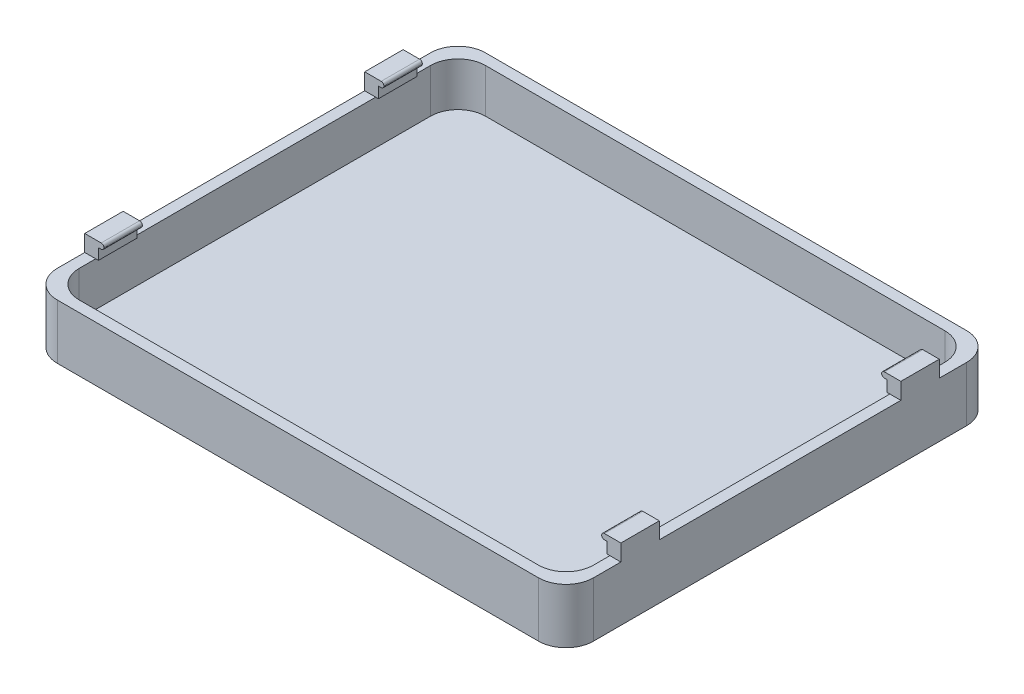
SolidWorks part; units mm, degrees
ref_plane "Front Plane" through (0, 0, 0) normal (0, 0, 1) x (1, 0, 0)
ref_plane "Top Plane" through (0, 0, 0) normal (0, 1, 0) x (1, 0, 0)
ref_plane "Right Plane" through (0, 0, 0) normal (1, 0, 0) x (0, 0, -1)
sketch "Sketch1" plane through (0, 0, 0) normal (0, 1, 0) x (1, 0, 0)
  line L1 (-48.85, 0) -> (48.85, 0)
  line L2 (-48.85, 0) -> (-48.85, -78.02)
  line L3 (-48.85, -78.02) -> (48.85, -78.02)
  line L4 (48.85, 0) -> (48.85, -78.02)
  point P4 (0, 0)
  dimension "D1" = 97.7
  dimension "D2" = 78.02
extrude "Boss-Extrude1" add sketch "Sketch1" along normal blind 10
sketch "Sketch2" plane through (0, 10, 0) normal (0, 1, 0) x (1, 0, 0)
  line L0 (-48.85, 0) -> (-48.85, -78.02) construction
  line L1 (-48.85, -10) -> (-46.35, -10)
  line L2 (-48.85, -10) -> (-48.85, -17)
  line L3 (-48.85, -17) -> (-46.35, -17)
  line L4 (-46.35, -10) -> (-46.35, -17)
  line L5 (48.85, 0) -> (-48.85, 0) construction
  line L6 (0, -5.5) -> (0, 5.5) construction
  line L7 (46.35, -10) -> (46.35, -17)
  line L8 (48.85, -17) -> (46.35, -17)
  line L9 (48.85, -10) -> (48.85, -17)
  line L10 (48.85, -10) -> (46.35, -10)
  line L11 (-76.3487, -39.01) -> (69.8401, -39.01) construction
  line L12 (48.85, 0) -> (-48.85, 0) construction
  line L13 (48.85, -68.02) -> (46.35, -68.02)
  line L14 (48.85, -68.02) -> (48.85, -61.02)
  line L15 (48.85, -61.02) -> (46.35, -61.02)
  line L16 (46.35, -68.02) -> (46.35, -61.02)
  line L17 (-46.35, -68.02) -> (-46.35, -61.02)
  line L18 (-48.85, -61.02) -> (-46.35, -61.02)
  line L19 (-48.85, -68.02) -> (-48.85, -61.02)
  line L20 (-48.85, -68.02) -> (-46.35, -68.02)
  dimension "D1" = 10
  dimension "D2" = 7
  dimension "D3" = 2.5
  dimension "D4" = 39.01
extrude "Boss-Extrude2" add sketch "Sketch2" along normal blind 3
sketch "Sketch3" plane through (-46.35, 0, 0) normal (1, 0, 0) x (0, 0, -1)
  line L0 (-10, 13) -> (-10, 10) construction
  line L1 (-17, 13) -> (-10, 13)
  line L2 (-17, 13) -> (-17, 12)
  line L3 (-17, 12) -> (-10, 12)
  line L4 (-10, 13) -> (-10, 12)
  line L5 (-61.02, 13) -> (-61.02, 10) construction
  line L6 (-68.02, 13) -> (-61.02, 13)
  line L7 (-68.02, 13) -> (-68.02, 12)
  line L8 (-68.02, 12) -> (-61.02, 12)
  line L9 (-61.02, 13) -> (-61.02, 12)
  dimension "D1" = 1
  dimension "D2" = 1
extrude "Boss-Extrude3" add sketch "Sketch3" along normal blind 1
sketch "Sketch4" plane through (46.35, 0, 0) normal (-1, 0, 0) x (0, 0, 1)
  line L1 (10, 13) -> (17, 13)
  line L2 (10, 13) -> (10, 12)
  line L3 (10, 12) -> (17, 12)
  line L4 (17, 13) -> (17, 12)
  line L6 (61.02, 13) -> (68.02, 13)
  line L7 (61.02, 13) -> (61.02, 12)
  line L8 (61.02, 12) -> (68.02, 12)
  line L9 (68.02, 13) -> (68.02, 12)
  line L10 (17, 13) -> (17, 10) construction
  line L12 (68.02, 13) -> (68.02, 10) construction
  point P5 (0, 0)
  point P12 (0, 0)
  point P13 (0, 0)
  point P15 (0, 0)
  dimension "D1" = 1
  dimension "D2" = 1
extrude "Boss-Extrude4" add sketch "Sketch4" along normal blind 1
fillet "Fillet1" radius 0.5 8 edges at (45.35, 13, 13.5) (45.35, 12, 13.5) (45.35, 12, 64.52) (45.35, 13, 64.52) (-45.35, 12, 13.5) (-45.35, 13, 13.5) (-45.35, 12, 64.52) (-45.35, 13, 64.52)
sketch "Sketch5" plane through (0, 10, 0) normal (0, 1, 0) x (1, 0, 0)
  line L0 (48.85, -61.02) -> (48.85, -17) construction
  line L1 (-46.85, -2) -> (46.85, -2)
  line L2 (-46.85, -2) -> (-46.85, -76.02)
  line L3 (-46.85, -76.02) -> (46.85, -76.02)
  line L4 (46.85, -2) -> (46.85, -76.02)
  line L5 (-48.85, -17) -> (-48.85, -61.02) construction
  line L6 (48.85, 0) -> (-48.85, 0) construction
  line L7 (-48.85, -78.02) -> (48.85, -78.02) construction
  dimension "D1" = 2
  dimension "D2" = 2
  dimension "D3" = 2
  dimension "D4" = 2
extrude "Cut-Extrude1" cut sketch "Sketch5" against normal offset from surface (8 mm away) 2 up to face at (0, 0, 39.01)
fillet "Fillet2" radius 5 8 edges at (48.85, 5, 0) (-48.85, 5, 0) (-48.85, 5, 78.02) (48.85, 5, 78.02) (46.85, 6, 76.02) (-46.85, 6, 76.02) (46.85, 6, 2) (-46.85, 6, 2)
